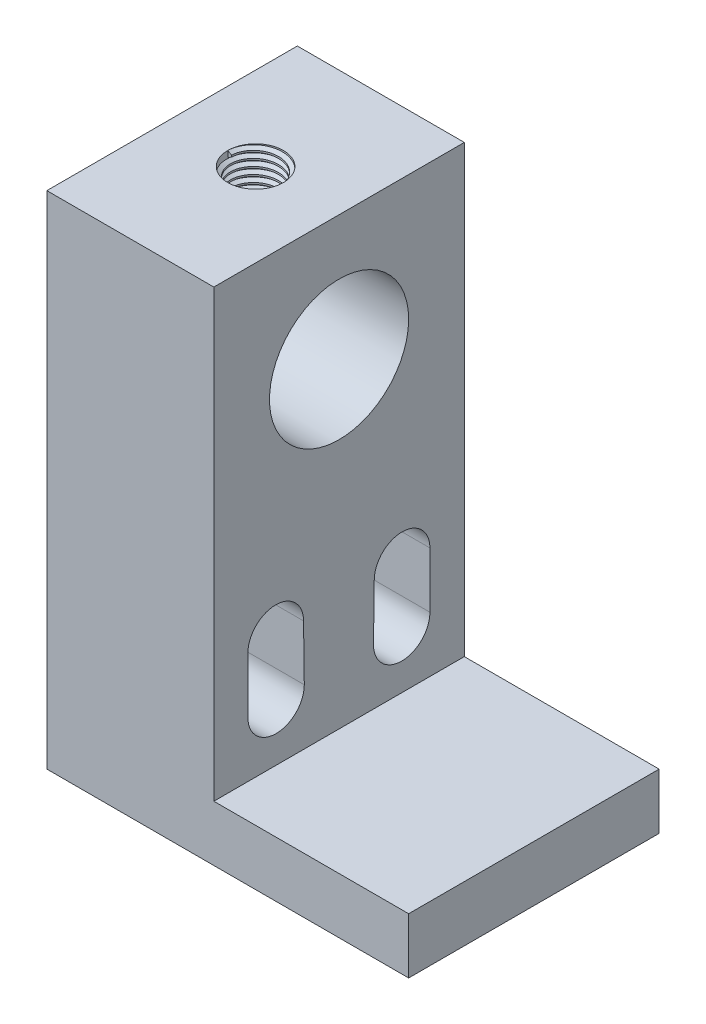
SolidWorks part; units mm, degrees
ref_plane "Plan de face" through (0, 0, 0) normal (0, 0, 1) x (1, 0, 0)
ref_plane "Plan de dessus" through (0, 0, 0) normal (0, 1, 0) x (1, 0, 0)
ref_plane "Plan de droite" through (0, 0, 0) normal (1, 0, 0) x (0, 0, -1)
sketch "Esquisse1" plane through (0, 0, 0) normal (0, 0, 1) x (1, 0, 0)
  line L0 (0, 0) -> (30, 0)
  line L3 (0, -90) -> (0, 0)
  line L4 (0, -90) -> (65, -90)
  line L5 (65, -90) -> (65, -80)
  line L6 (65, -80) -> (30, -80)
  line L7 (30, -80) -> (30, 0)
extrude "Boss.-Extru.1" add sketch "Esquisse1" along normal blind 45
sketch "Esquisse2" plane through (30, 0, 0) normal (1, 0, 0) x (0, 0, -1)
  circle A0 centre (-22.5, -22.5) radius 12.5
  point P0 (-22.5, -23.4136)
extrude "Enlèv. mat.-Extru.1" cut sketch "Esquisse2" against normal blind 45
sketch "Esquisse3" plane through (30, 0, 0) normal (1, 0, 0) x (0, 0, -1)
  line L0 (-38.8854, -70) -> (-38.8854, -60)
  line L2 (-28.8854, -60) -> (-28.75, -70)
  line L8 (-6.1823, -70) -> (-6.1823, -60)
  line L10 (-16.1823, -60) -> (-16.3177, -70)
  arc A2 (-38.8854, -60) -> (-28.8854, -60) centre (-33.8854, -60) cw
  arc A3 (-38.8854, -70) -> (-28.75, -70) centre (-33.8177, -70) ccw
  arc A6 (-6.1823, -60) -> (-16.1823, -60) centre (-11.1823, -60) ccw
  arc A7 (-6.1823, -70) -> (-16.3177, -70) centre (-11.25, -70) cw
extrude "Enlèv. mat.-Extru.2" cut sketch "Esquisse3" against normal blind 45
sketch "Esquisse4" plane through (0, 0, 0) normal (0, 1, 0) x (1, 0, 0)
  circle A0 centre (15, -22.5) radius 5
extrude "Enlèv. mat.-Extru.3" cut sketch "Esquisse4" against normal blind 25
thread "Filetage1" pitch 1.25 method extrude profile "Profil de filetage1" start angle 0, offset 0, length 10, pitch 1.25, diameter 10
ref_plane "Plan1" through (10, 0, 22.5) normal (0, 0, 1) x (-1, 0, 0)
sketch "Profil de filetage1" plane through (10, 0, 22.5) normal (0, 0, 1) x (-1, 0, 0)
  line L0 (0, 0) -> (0, 1.25) construction
  line L11 (0, 0) -> (0, 1.0937)
  line L12 (0, 1.0937) -> (-0.6766, 0.7031)
  line L13 (-0.6766, 0.7031) -> (-0.6766, 0.3906)
  line L15 (-0.6766, 0.3906) -> (0, 0)
  line L17 (-0.6766, 0.5469) -> (0, 0.5469) construction
  point P2 (0, 0)
  dimension "Pitch" = 1.25
  dimension "Profile_Angle" = 60
  dimension "Profile_Land" = 0.3125
  dimension "Profile_Height" = 0.6766
